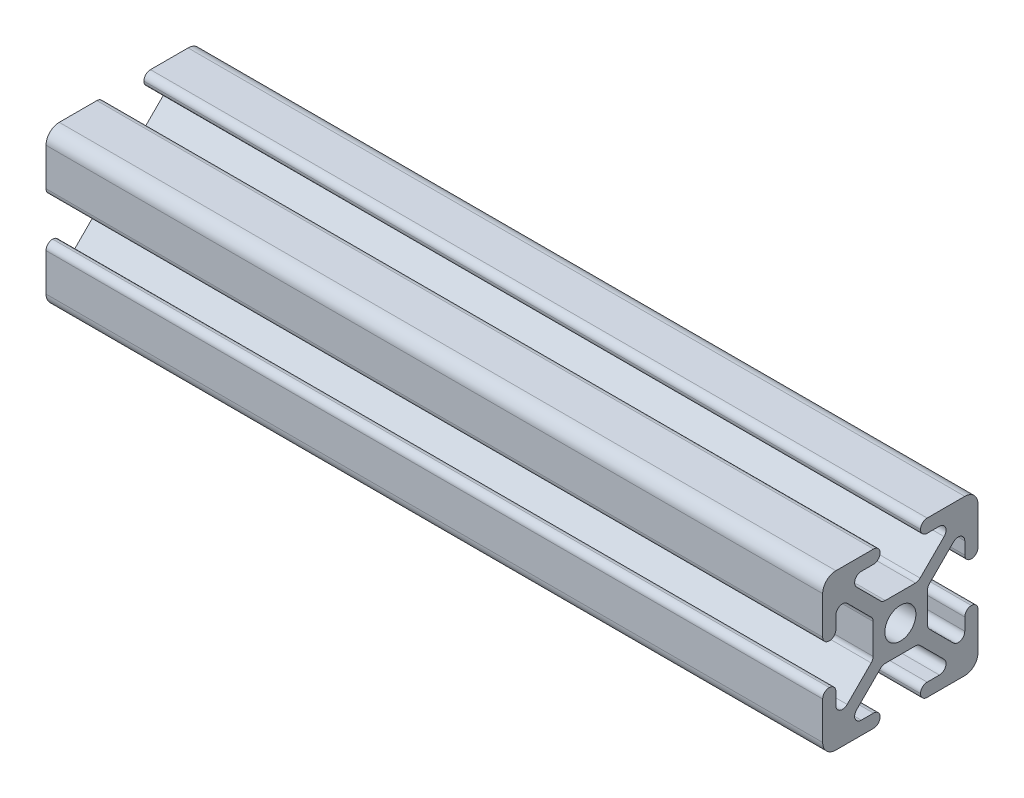
SolidWorks part; units mm, degrees
ref_plane "Front Plane" through (0, 0, 0) normal (1, 0, 0) x (0, 1, 0)
ref_plane "Top Plane" through (0, 0, 0) normal (0, 0, 1) x (0, 1, 0)
ref_plane "Right Plane" through (0, 0, 0) normal (0, 1, 0) x (-1, 0, 0)
sketch "Sketch1" plane through (0, 0, 0) normal (1, 0, 0) x (0, 1, 0)
  line L0 (0, 0) -> (0, 12.5) construction
  line L1 (-12.5, -12.5) -> (12.5, -12.5)
  line L2 (-12.5, -12.5) -> (-12.5, 12.5)
  line L3 (-12.5, 12.5) -> (12.5, 12.5)
  line L4 (12.5, -12.5) -> (12.5, 12.5)
  line L5 (-12.5, -12.5) -> (12.5, 12.5) construction
  line L6 (-12.5, 12.5) -> (12.5, -12.5) construction
  line L7 (-3.25, 12.5) -> (-3.25, 10.37)
  line L8 (-3.25, 10.37) -> (-8.8639, 10.37)
  line L9 (-8.8639, 10.37) -> (-2.8739, 4.38)
  line L10 (-2.8739, 4.38) -> (2.8739, 4.38)
  line L11 (8.8639, 10.37) -> (2.8739, 4.38)
  line L12 (3.25, 10.37) -> (8.8639, 10.37)
  line L13 (3.25, 12.5) -> (3.25, 10.37)
  line L14 (12.5, -3.25) -> (10.37, -3.25)
  line L15 (10.37, -3.25) -> (10.37, -8.8639)
  line L16 (10.37, -8.8639) -> (4.38, -2.8739)
  line L17 (4.38, 2.8739) -> (4.38, -2.8739)
  line L18 (10.37, 8.8639) -> (4.38, 2.8739)
  line L19 (10.37, 3.25) -> (10.37, 8.8639)
  line L20 (12.5, 3.25) -> (10.37, 3.25)
  line L21 (-3.25, -12.5) -> (-3.25, -10.37)
  line L22 (-3.25, -10.37) -> (-8.8639, -10.37)
  line L23 (-8.8639, -10.37) -> (-2.8739, -4.38)
  line L24 (2.8739, -4.38) -> (-2.8739, -4.38)
  line L25 (8.8639, -10.37) -> (2.8739, -4.38)
  line L26 (3.25, -10.37) -> (8.8639, -10.37)
  line L27 (3.25, -12.5) -> (3.25, -10.37)
  line L28 (-12.5, 3.25) -> (-10.37, 3.25)
  line L29 (-10.37, 3.25) -> (-10.37, 8.8639)
  line L30 (-10.37, 8.8639) -> (-4.38, 2.8739)
  line L31 (-4.38, -2.8739) -> (-4.38, 2.8739)
  line L32 (-10.37, -8.8639) -> (-4.38, -2.8739)
  line L33 (-10.37, -3.25) -> (-10.37, -8.8639)
  line L34 (-12.5, -3.25) -> (-10.37, -3.25)
  circle A0 centre (0, 0) radius 2.5
  point P0 (0, 0)
  point P15 (0, 4.38)
  dimension "D3" = 5
  dimension "D1" = 25
  dimension "D2" = 25
  dimension "D4" = 2.13
  dimension "D5" = 2.13
  dimension "D6" = 6.5
  dimension "D7" = 4.38
  dimension "D8" = 4
extrude "Boss-Extrude1" add sketch "Sketch1" along normal blind 125 contours L34 L2 L1 L21 L22 L23 L24 L25 L26 L27 L4 L14 L15 L16 L17 L18 L19 L20 L3 L13 L12 L11 L10 L9 L8 L7 L28 L29 L30 L31 L32 L33 A0 region at (0, -12.1464, -7.875)
fillet "Fillet1" radius 1.065 32 edges at (62.5, -10.37, -8.8639) (62.5, 2.8739, -4.38) (62.5, -2.8739, -4.38) (62.5, -4.38, 2.8739) (62.5, -4.38, -2.8739) (62.5, -2.8739, 4.38) (62.5, 2.8739, 4.38) (62.5, 4.38, 2.8739) (62.5, 4.38, -2.8739) (62.5, -8.8639, -10.37) (62.5, 8.8639, -10.37) (62.5, 10.37, -8.8639) (62.5, -10.37, 8.8639) (62.5, -8.8639, 10.37) (62.5, 10.37, 8.8639) (62.5, 8.8639, 10.37) (62.5, 12.5, 3.25) (62.5, -3.25, -12.5) (62.5, -10.37, 3.25) (62.5, 10.37, 3.25) (62.5, -10.37, -3.25) (62.5, -12.5, -3.25) (62.5, -12.5, 3.25) (62.5, 3.25, -10.37) (62.5, -3.25, -10.37) (62.5, 3.25, -12.5) (62.5, 10.37, -3.25) (62.5, 12.5, -3.25) (62.5, 3.25, 12.5) (62.5, 3.25, 10.37) (62.5, -3.25, 10.37) (62.5, -3.25, 12.5)
fillet "Fillet2" radius 2.13 4 edges at (62.5, 12.5, -12.5) (62.5, -12.5, -12.5) (62.5, 12.5, 12.5) (62.5, -12.5, 12.5)
